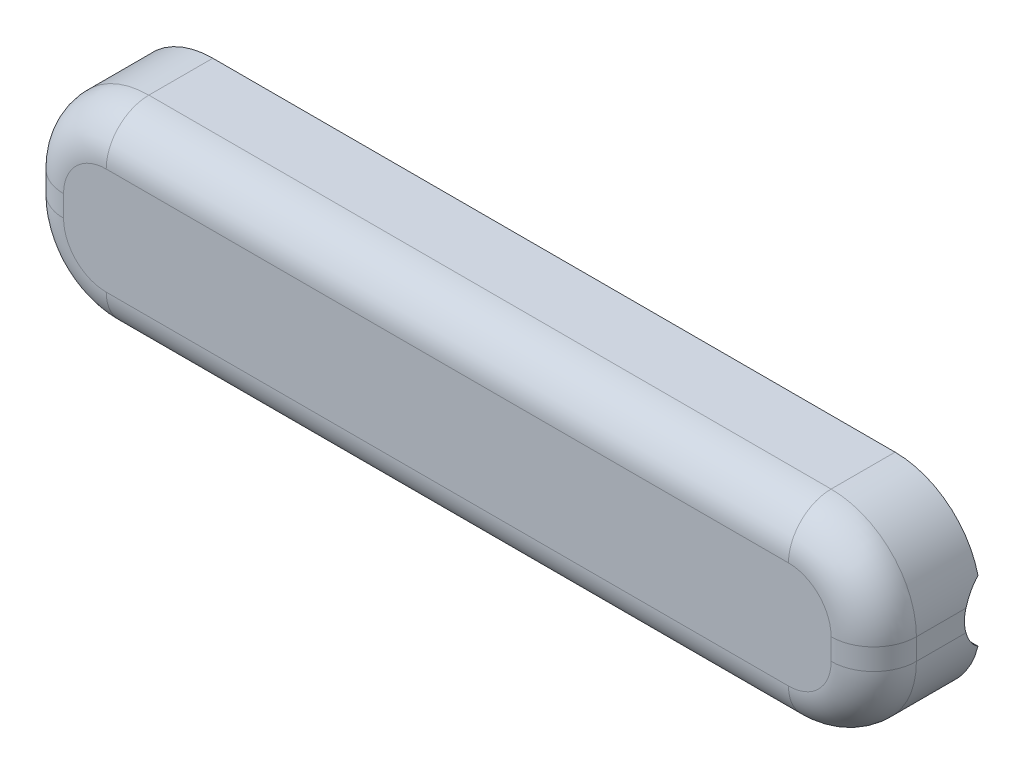
SolidWorks part; units mm, degrees
ref_plane "Alzado" through (0, 0, 0) normal (0, 0, 1) x (1, 0, 0)
ref_plane "Planta" through (0, 0, 0) normal (0, 1, 0) x (1, 0, 0)
ref_plane "Vista lateral" through (0, 0, 0) normal (1, 0, 0) x (0, 0, -1)
sketch "Croquis1" plane through (0, 0, 0) normal (0, 0, 1) x (1, 0, 0)
  line L1 (-127, 28.575) -> (127, 28.575)
  line L2 (-127, 28.575) -> (-127, -28.575)
  line L3 (-127, -28.575) -> (127, -28.575)
  line L4 (127, 28.575) -> (127, -28.575)
  line L5 (-127, 28.575) -> (127, -28.575) construction
  line L6 (-127, -28.575) -> (127, 28.575) construction
  point P0 (0, 0)
  dimension "D1" = 254
  dimension "D2" = 57.15
extrude "Saliente-Extruir1" add sketch "Croquis1" along normal blind 31.75
fillet "Redondeo1" radius 12.7 4 edges at (127, 0, 31.75) (0, -28.575, 31.75) (0, 28.575, 31.75) (-127, 0, 31.75)
fillet "Redondeo2" radius 25.4 8 edges at (-123.2803, 24.8553, 28.0303) (-123.2803, -24.8553, 28.0303) (123.2803, -24.8553, 28.0303) (123.2803, 24.8553, 28.0303) (127, 28.575, 9.525) (127, -28.575, 9.525) (-127, -28.575, 9.525) (-127, 28.575, 9.525)
sketch "Croquis2" plane through (0, 0, 0) normal (1, 0, 0) x (0, 0, -1)
  line L0 (0, 0) -> (6.35, 0) construction
  circle A0 centre (6.35, 0) radius 11.1125
  dimension "D2" = 22.225
  dimension "D1" = 6.35
extrude "Cortar-Extruir1" cut sketch "Croquis2" against normal through all both and the other way through all
